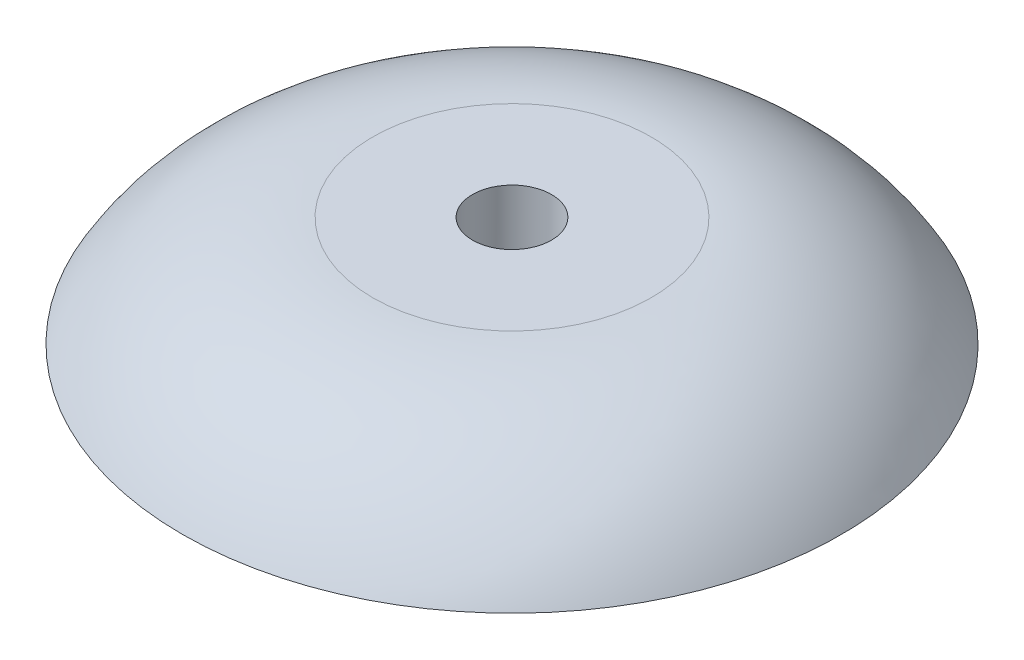
SolidWorks part; units mm, degrees
ref_plane "Front Plane" through (0, 0, 0) normal (0, 0, 1) x (1, 0, 0)
ref_plane "Top Plane" through (0, 0, 0) normal (0, 1, 0) x (1, 0, 0)
ref_plane "Right Plane" through (0, 0, 0) normal (1, 0, 0) x (0, 0, -1)
sketch "Sketch2" plane through (0, 0, 0) normal (0, 1, 0) x (1, 0, 0)
  circle A0 centre (0, 0) radius 15
  dimension "D1" = 30
extrude "Boss-Extrude1" add sketch "Sketch2" along normal blind 5
sketch "Sketch3" plane through (0, 0, 0) normal (0, -1, 0) x (1, 0, 0)
  circle A0 centre (0, 0) radius 10
  dimension "D1" = 20
extrude "Cut-Extrude1" cut sketch "Sketch3" against normal blind 2
sketch "Sketch4" plane through (0, 5, 0) normal (0, 1, 0) x (1, 0, 0)
  circle A0 centre (0, 0) radius 1.7
  point P0 (0, 0)
  dimension "D1" = 3.4
hole_wizard "M3 Clearance Hole1" positions "Sketch4" profile "Sketch5" hole size "M3" standard "ANSI Metric" end condition through all
sketch "Sketch5" plane through (0, 5, 0) normal (1, 0, 0) x (0, 0, 1)
  line L0 (0, 0) -> (0, 5)
  line L1 (0, 5) -> (1.8, 5)
  line L2 (1.8, 5) -> (1.8, 0)
  line L5 (1.8, 0) -> (0, 0)
  line L11 (0, -6.35) -> (0, 107.95) construction
  dimension "Thru Hole Dia." = 3.6
  dimension "Thru Hole Depth" = 5
fillet "Fillet1" radius 10 1 edges at (0, 5, 15)
